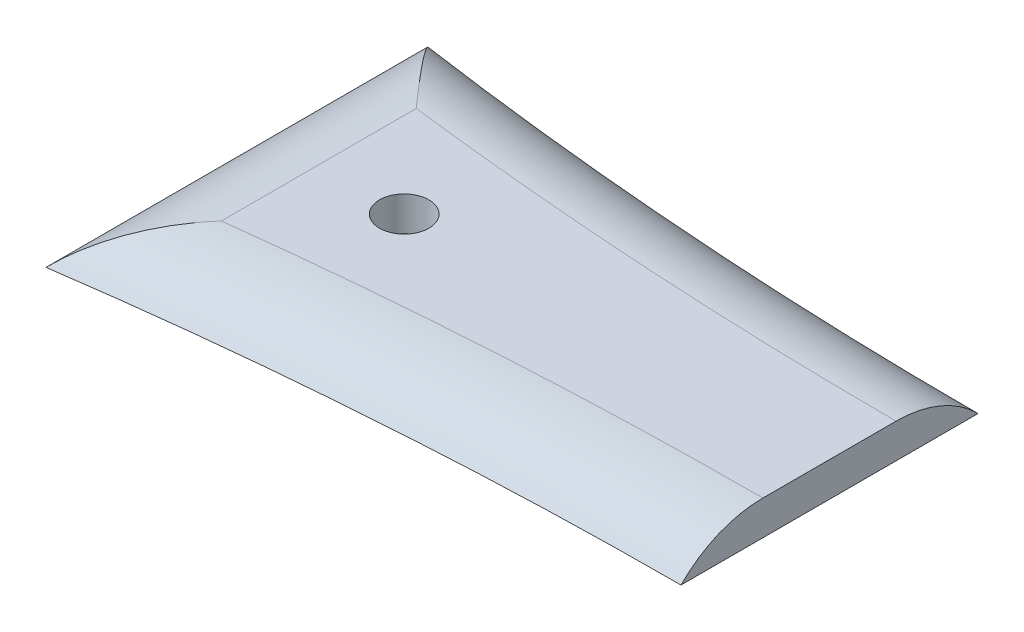
SolidWorks part; units mm, degrees
ref_plane "Front Plane" through (0, 0, 0) normal (0, 0, 1) x (1, 0, 0)
ref_plane "Top Plane" through (0, 0, 0) normal (0, 1, 0) x (1, 0, 0)
ref_plane "Right Plane" through (0, 0, 0) normal (1, 0, 0) x (0, 0, -1)
sketch "Sketch1" plane through (0, 0, 0) normal (0, 1, 0) x (1, 0, 0)
  line L0 (-42.5547, 14.2429) -> (-42.5547, -6.7571)
  line L1 (-42.5547, -6.7571) -> (-1.5547, -6.7571)
  line L2 (-1.5547, -6.7571) -> (-1.5547, 14.2429)
  line L3 (-1.5547, 14.2429) -> (-42.5547, 14.2429)
  line L4 (-50.5547, 22.2429) -> (-50.5547, -14.7571)
  line L5 (-50.5547, -14.7571) -> (6.4453, -14.7571)
  line L6 (6.4453, -14.7571) -> (6.4453, 22.2429)
  line L7 (6.4453, 22.2429) -> (-50.5547, 22.2429)
  line L8 (6.4453, 3.7429) -> (-22.0547, 3.7429)
  line L11 (-22.0547, 3.7429) -> (6.4453, 3.7429)
  line L12 (132.9453, 22.2429) -> (132.9453, -14.7571)
  circle A0 centre (2.4453, 8.7429) radius 1.7
  circle A1 centre (2.4453, -1.2571) radius 1.7
  circle A2 centre (-46.5547, -1.2571) radius 1.7
  circle A3 centre (-46.5547, 8.7429) radius 1.7
  arc A4 (6.4453, 22.2429) -> (132.9453, 22.2429) centre (69.6953, 379.6894) ccw
  arc A5 (6.4453, -14.7571) -> (132.9453, -14.7571) centre (69.6953, -372.2036) cw
  point P22 (132.9453, 3.7429)
  dimension "D4" = 3.4
  dimension "D1" = 8
  dimension "D2" = 21
  dimension "D3" = 41
extrude "Boss-Extrude1" add sketch "Sketch1" along normal blind 16 contours L6 A5 L12 A4 | L6 L2 L1 L0 L3 L7 L4 L5 A2 A1 A0 A3 region at (5.7657, 0, 5.5071) region at (69.6953, 0, -3.7429)
sketch "Sketch2" plane through (0, 16, 0) normal (0, 1, 0) x (1, 0, 0)
  line L8 (-22.0547, -6.7571) -> (-22.0547, -2.3508)
  line L9 (-42.5547, -6.7571) -> (-1.5547, -6.7571) construction
  line L10 (6.4453, -6.7571) -> (-50.5547, -6.7571)
  line L11 (-50.5547, 22.2429) -> (-50.5547, -14.7571) construction
  line L12 (-42.5547, 3.7429) -> (-38.9164, 3.7429)
  line L13 (-42.5547, 14.2429) -> (-42.5547, -6.7571) construction
  line L14 (6.4453, 14.2429) -> (-50.5547, 14.2429)
  line L15 (-50.5547, -6.7571) -> (-50.5547, 14.2429)
  line L16 (6.4453, 14.2429) -> (6.4453, -6.7571)
  line M6 (-50.5547, 22.2429) -> (-50.5547, -14.7571)
  line M10 (-42.5547, 14.2429) -> (-1.5547, 14.2429)
  line M11 (-1.5547, 14.2429) -> (-1.5547, -6.7571)
  line M12 (-1.5547, -6.7571) -> (-42.5547, -6.7571)
  line M13 (-42.5547, -6.7571) -> (-42.5547, 14.2429)
  circle M14 centre (-46.5547, -1.2571) radius 1.7
  circle M15 centre (2.4453, -1.2571) radius 1.7
  circle M16 centre (2.4453, 8.7429) radius 1.7
  circle M17 centre (-46.5547, 8.7429) radius 1.7
extrude "Cut-Extrude1" cut sketch "Sketch2" against normal blind 6 contours M10 M13 M12 M11 | L14 L10 M13 M6 M17 M14 | L16 L14 L10 M11 M16 M15 region at (2.4453, 16, -3.7429) region at (-22.0547, 16, -3.7429) region at (-46.5547, 16, -3.7429)
sketch "Sketch3" plane through (0, 16, 0) normal (0, 1, 0) x (1, 0, 0)
  line L0 (132.9453, -8.2571) -> (132.9453, 15.7429)
  line L1 (132.9453, 22.2429) -> (132.9453, -14.7571) construction
  line L2 (105.9453, 3.7429) -> (105.9453, 15.7429)
  line L3 (105.9453, 3.7429) -> (105.9453, -8.2571)
  line L4 (105.9453, -8.2571) -> (132.9453, -8.2571)
  line L6 (132.9453, 15.7429) -> (105.9453, 15.7429)
  line L7 (105.9453, 15.7429) -> (122.4453, 15.7429)
  line L8 (127.4453, 15.7429) -> (127.4453, 23.7526)
  line L9 (127.4453, 23.7526) -> (122.4453, 23.7526)
  line L10 (122.4453, 23.7526) -> (122.4453, 15.7429)
  line L11 (122.4453, 15.7429) -> (127.4453, 15.7429)
  line L12 (132.9453, 3.7429) -> (129.8323, 3.7429)
  line L13 (122.4453, -8.2571) -> (127.4453, -8.2571)
  line L14 (122.4453, -16.2668) -> (122.4453, -8.2571)
  line L15 (127.4453, -16.2668) -> (122.4453, -16.2668)
  line L16 (127.4453, -8.2571) -> (127.4453, -16.2668)
  arc M12 (6.4453, -14.7571) -> (132.9453, -14.7571) centre (69.6953, -372.2036) cw
  line M13 (132.9453, -14.7571) -> (132.9453, 22.2429)
  arc M14 (132.9453, 22.2429) -> (6.4453, 22.2429) centre (69.6953, 379.6894) cw
  dimension "D1" = 27
extrude "Cut-Extrude3" cut sketch "Sketch3" against normal blind 13 contours L10 L6 L8 M14 | L16 L4 L14 M12 | L0 L6 L7 L2 L3 L4 M13 region at (119.4453, 16, -3.7429) region at (125.0072, 16, 10.8516) region at (125.0072, 16, -18.3373)
ref_plane "Plane1" through (0, 106, 0) normal (0, 1, 0) x (1, 0, 0)
fillet "Fillet3" radius 10 2 edges at (-50.5547, 8, 14.7571) (-50.5547, 8, -22.2429)
sketch "Sketch4" plane through (0, 106, 0) normal (0, 1, 0) x (1, 0, 0)
  line L0 (18.0294, 20.3856) -> (18.0294, -12.8998)
  line L1 (132.9453, 22.2429) -> (132.9453, -14.7571)
  arc A0 (6.4453, 22.2429) -> (122.4453, 20.5432) centre (69.6953, 379.6894) ccw construction
  arc A1 (122.4453, -13.0574) -> (6.4453, -14.7571) centre (69.6953, -372.2036) ccw construction
  arc A2 (18.0294, -12.8998) -> (132.9453, -14.7571) centre (69.6953, -372.2036) cw
  arc A3 (18.0294, 20.3856) -> (132.9453, 22.2429) centre (69.6953, 379.6894) ccw
ref_plane "Plane2" through (0, 16, 0) normal (0, 1, 0) x (1, 0, 0)
sketch "Sketch9" plane through (0, 0, 0) normal (0, -1, 0) x (1, 0, 0)
  text T0 "<b>BINUS ASO</b>" font "Century Gothic" height in points 48
extrude "Cut-Extrude6" cut sketch "Sketch9" against normal blind 5
extrude "Boss-Extrude2" add sketch "Sketch4" along normal blind 3 separate body
fillet "Fillet1" radius 10 4 edges at (132.9453, 109, -3.7429) (75.5613, 109, 9.2516) (18.0294, 109, -3.7429) (75.5613, 109, -16.7374)
fillet "Fillet2" radius 10 rebuild error yes
sketch "Sketch10" plane through (0, 109, 0) normal (0, 1, 0) x (1, 0, 0)
  line L0 (25.1709, 3.7429) -> (95.1334, 3.7429)
  line L1 (25.1709, 12.2363) -> (25.1709, -4.7505) construction
  circle A0 centre (32.6164, 3.7429) radius 2.15
  circle A1 centre (95.1334, 3.7429) radius 2.15
  dimension "D1" = 4.3
  dimension "D2" = 4.3
extrude "Cut-Extrude7" cut sketch "Sketch10" against normal blind 105 contours A0 | A1
ref_plane "Plane3" through (0, 0, 100) normal (0, 0, 1) x (1, 0, 0)
sketch "Sketch11" plane through (0, 0, 100) normal (0, 0, 1) x (1, 0, 0)
  line L1 (-76.6665, 39.3422) -> (169.897, 39.3422)
  line L2 (-76.6665, 39.3422) -> (-76.6665, -19.7567)
  line L3 (-76.6665, -19.7567) -> (169.897, -19.7567)
  line L4 (169.897, 39.3422) -> (169.897, -19.7567)
extrude "Cut-Extrude8" cut sketch "Sketch11" against normal blind 145
sketch "Sketch12" plane through (0, 106, 0) normal (0, -1, 0) x (1, 0, 0)
  line L0 (132.9453, -3.7429) -> (69.6953, -3.7429)
  line L1 (132.9453, 14.7571) -> (132.9453, -22.2429) construction
  line L2 (69.6953, -3.7429) -> (69.6953, 21.0947)
  line L3 (69.6953, 21.0947) -> (147.9921, 21.0947)
  line L4 (147.9921, 21.0947) -> (147.9921, -29.7425)
  line L5 (147.9921, -29.7425) -> (69.6953, -29.7425)
  line L6 (69.6953, -29.7425) -> (69.6953, -3.7429)
  circle M3 centre (95.1334, -3.7429) radius 2.15
  arc M4 (18.0294, -20.3856) -> (132.9453, -22.2429) centre (69.6953, -379.6894) cw
  line M5 (132.9453, -22.2429) -> (132.9453, 14.7571)
  arc M6 (132.9453, 14.7571) -> (18.0294, 12.8998) centre (69.6953, 372.2036) cw
  dimension "D1" = 63.25
extrude "Cut-Extrude9" cut sketch "Sketch12" against normal blind 26 contours L6 L5 L4 L3 L2 M6 M5 M4 | L2 L0 M3 M5 M6 | L6 L0 M4 M5 M3 region at (103.3597, 106, -11.2829) region at (133.8788, 106, 5.5071) region at (103.3597, 106, 3.7972)
